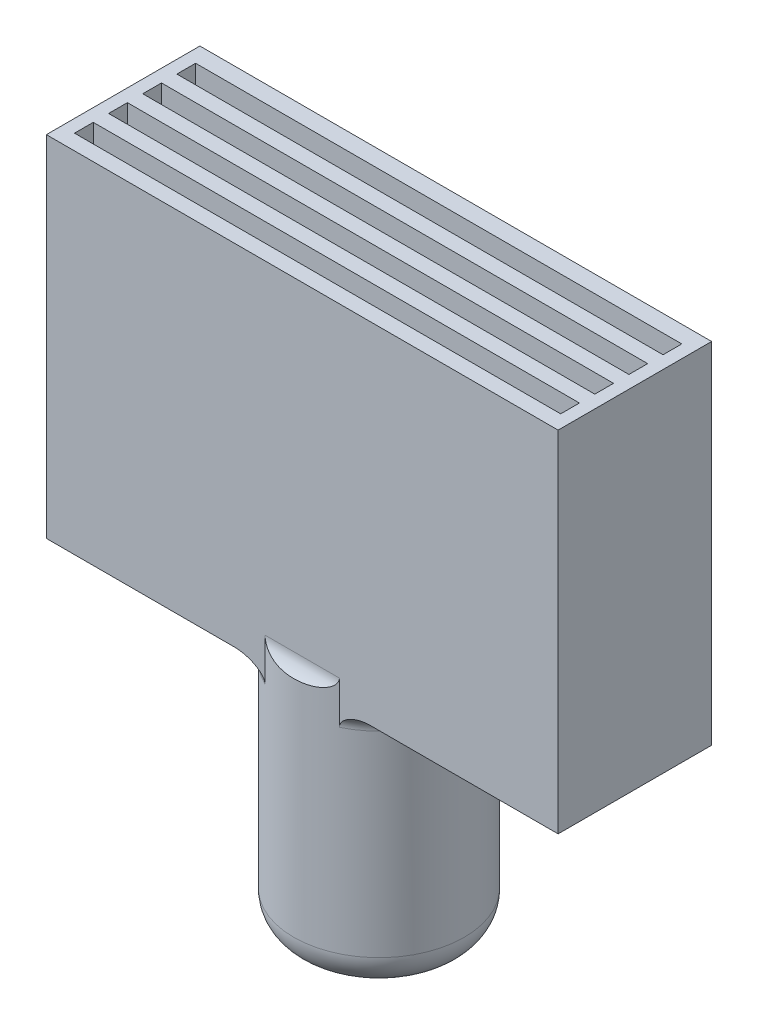
SolidWorks part; units mm, degrees
ref_plane "Front Plane" through (0, 0, 0) normal (0, 0, 1) x (1, 0, 0)
ref_plane "Top Plane" through (0, 0, 0) normal (0, 1, 0) x (1, 0, 0)
ref_plane "Right Plane" through (0, 0, 0) normal (1, 0, 0) x (0, 0, -1)
sketch "Sketch1" plane through (0, 0, 0) normal (0, 1, 0) x (1, 0, 0)
  circle A0 centre (0, 0) radius 10
  dimension "D1" = 20
extrude "Boss-Extrude1" add sketch "Sketch1" along normal blind 30
fillet "Fillet1" radius 4 1 edges at (0, 0, 10)
sketch "Sketch2" plane through (0, 30, 0) normal (0, 1, 0) x (1, 0, 0)
  line L0 (-28.5, 3) -> (28.5, 3)
  line L1 (-30, -9) -> (30, -9)
  line L2 (-30, -9) -> (-30, 9)
  line L3 (-30, 9) -> (30, 9)
  line L4 (30, -9) -> (30, 9)
  line L5 (-30, -9) -> (30, 9) construction
  line L6 (-30, 9) -> (30, -9) construction
  line L7 (-28.5, 7) -> (28.5, 7)
  line L8 (-28.5, 7) -> (-28.5, 4.8)
  line L9 (-28.5, 4.8) -> (28.5, 4.8)
  line L10 (28.5, 7) -> (28.5, 4.8)
  line L11 (-28.5, 3) -> (-28.5, 0.8)
  line L12 (-28.5, 0.8) -> (28.5, 0.8)
  line L13 (28.5, 3) -> (28.5, 0.8)
  line L14 (-28.5, -1) -> (28.5, -1)
  line L15 (-28.5, -1) -> (-28.5, -3.2)
  line L16 (-28.5, -3.2) -> (28.5, -3.2)
  line L17 (28.5, -1) -> (28.5, -3.2)
  line L18 (-28.5, -5) -> (28.5, -5)
  line L19 (-28.5, -5) -> (-28.5, -7.2)
  line L20 (-28.5, -7.2) -> (28.5, -7.2)
  line L21 (28.5, -5) -> (28.5, -7.2)
  point P0 (0, 0)
  dimension "D1" = 18
  dimension "D2" = 60
  dimension "D3" = 2.2
  dimension "D4" = 57
  dimension "D5" = 1.5
  dimension "D6" = 2
  dimension "D7" = 4
extrude "Boss-Extrude2" add sketch "Sketch2" along normal blind 40
sketch "Sketch3" plane through (0, 30, 0) normal (0, -1, 0) x (1, 0, 0)
  line L1 (30, -9) -> (-30, -9)
  line L2 (30, -9) -> (30, 9)
  line L3 (30, 9) -> (-30, 9)
  line L4 (-30, -9) -> (-30, 9)
extrude "Boss-Extrude3" add sketch "Sketch3" along normal blind 1
fillet "Fillet2" radius 2 2 edges at (-10, 29, 0) (10, 29, 0)
fillet "Fillet3" radius 2 2 edges at (0, 30, 9) (0, 30, -9)
